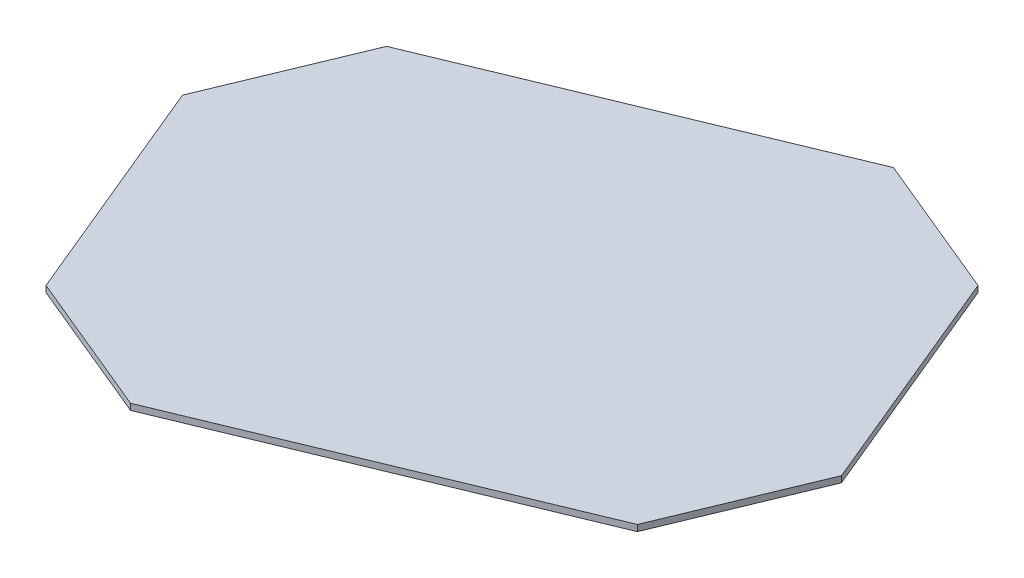
SolidWorks part; units mm, degrees
ref_plane "Front Plane" through (0, 0, 0) normal (0, 0, 1) x (1, 0, 0)
ref_plane "Top Plane" through (0, 0, 0) normal (0, 1, 0) x (1, 0, 0)
ref_plane "Right Plane" through (0, 0, 0) normal (1, 0, 0) x (0, 0, -1)
sketch "Sketch1" plane through (0, 0, 0) normal (0, 1, 0) x (1, 0, 0)
  line L0 (112.3068, 112.3068) -> (42.7387, 141.1229)
  line L1 (-158.8258, 0) -> (-112.3068, -112.3068) construction
  line L2 (-112.3068, -112.3068) -> (0, -158.8258) construction
  line L3 (0, -158.8258) -> (112.3068, -112.3068) construction
  line L4 (112.3068, -112.3068) -> (158.8258, 0) construction
  line L5 (158.8258, 0) -> (112.3068, 112.3068) construction
  line L6 (112.3068, 112.3068) -> (0, 158.8258) construction
  line L7 (0, 158.8258) -> (-112.3068, 112.3068) construction
  line L8 (-112.3068, 112.3068) -> (-158.8258, 0) construction
  line L9 (-158.8258, 0) -> (-130.0097, 69.5681)
  line L10 (158.8258, 0) -> (130.0097, -69.5681)
  line L11 (-112.3068, -112.3068) -> (-42.7387, -141.1229)
  line L12 (42.7387, 141.1229) -> (-130.0097, 69.5681)
  line L13 (130.0097, -69.5681) -> (-42.7387, -141.1229)
  line L14 (112.3068, 112.3068) -> (158.8258, 0)
  line L15 (-158.8258, 0) -> (-112.3068, -112.3068)
  circle A0 centre (0, 0) radius 146.7359 construction
  dimension "D1" = 121.56
extrude "Boss-Extrude1" add sketch "Sketch1" along normal blind 3
